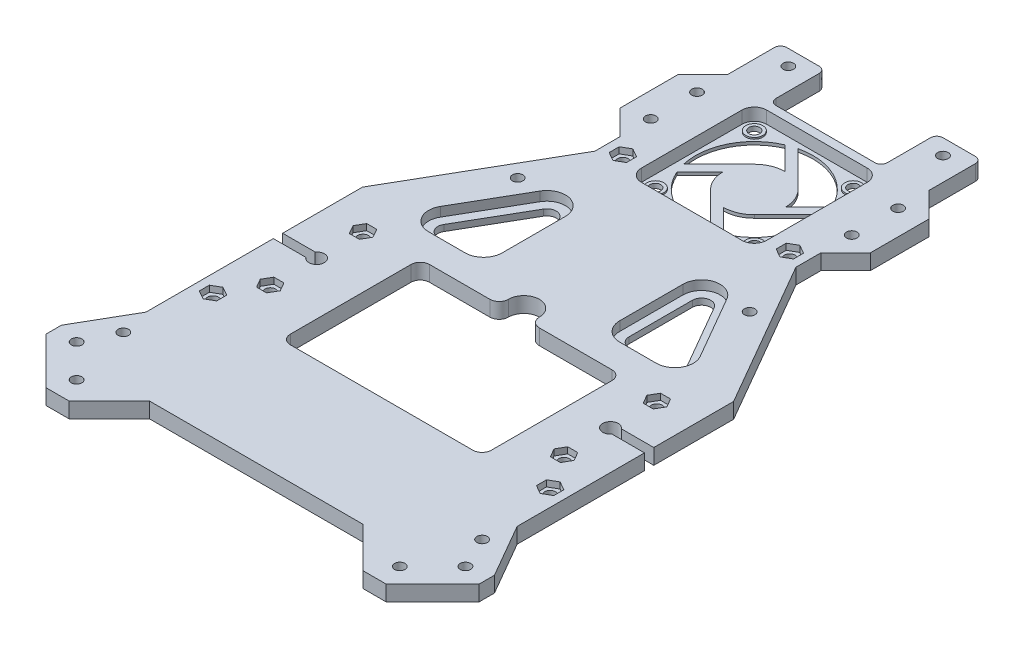
SolidWorks part; units mm, degrees
material "ABS PC"
ref_plane "Front Plane" through (0, 0, 0) normal (0, 0, 1) x (1, 0, 0)
ref_plane "Top Plane" through (0, 0, 0) normal (0, 1, 0) x (1, 0, 0)
ref_plane "Right Plane" through (0, 0, 0) normal (1, 0, 0) x (0, 0, -1)
sketch "Sketch1" plane through (0, 0, 0) normal (0, 1, 0) x (1, 0, 0)
  line L1 (70, -110) -> (-70, -110)
  line L2 (70, -110) -> (70, 110)
  line L3 (70, 110) -> (-70, 110)
  line L4 (-70, -110) -> (-70, 110)
  line L5 (70, -110) -> (-70, 110) construction
  line L6 (70, 110) -> (-70, -110) construction
  point P0 (0, 0)
  dimension "D1" = 220
  dimension "D2" = 140
extrude "Boss-Extrude1" add sketch "Sketch1" along normal blind 5
sketch "Sketch8" plane through (0, 5, 0) normal (0, 1, 0) x (1, 0, 0)
  line L0 (-70, 110) -> (-32.5, 110)
  line L1 (70, 110) -> (-70, 110) construction
  line L2 (-32.5, 110) -> (-32.5, 44.9519)
  line L3 (-32.5, 44.9519) -> (-70, -20)
  line L4 (-70, 110) -> (-70, -110) construction
  line L5 (-70, 110) -> (-70, -20)
  line L6 (0, 110) -> (0, -110) construction
  line L7 (-70, -110) -> (70, -110) construction
  line L8 (70, 110) -> (70, -20)
  line L9 (32.5, 44.9519) -> (70, -20)
  line L10 (32.5, 110) -> (32.5, 44.9519)
  line L11 (70, 110) -> (32.5, 110)
  dimension "D1" = 130
  dimension "D2" = 30
  dimension "D3" = 65
extrude "Cut-Extrude1" cut sketch "Sketch8" against normal blind 5
chamfer "Chamfer3" distance 15 angle 45 2 edges at (70, 2.5, 110) (-70, 2.5, 110)
sketch "Sketch48" plane through (0, 5, 0) normal (0, 1, 0) x (1, 0, 0)
  line L0 (32.5, 110) -> (-32.5, 110) construction
  line L1 (34.2449, 70.5) -> (40.5, 70.5) construction
  line L2 (32.5, 53) -> (32.5, 88)
  line L4 (32.5, 88) -> (40.5, 80)
  line L5 (40.5, 80) -> (40.5, 61)
  line L6 (32.5, 53) -> (40.5, 61)
  line L7 (0, 71.0199) -> (0, 60.9015) construction
  line L8 (-32.5, 53) -> (-40.5, 61)
  line L9 (-40.5, 80) -> (-40.5, 61)
  line L10 (-32.5, 88) -> (-40.5, 80)
  line L11 (-32.5, 53) -> (-32.5, 88)
  line L13 (32.5, 110) -> (32.5, 44.9519) construction
  point P16 (-32.5, 70.5)
  dimension "D1" = 45
  dimension "D2" = 8
  dimension "D3" = 35
  dimension "D4" = 39.5
extrude "Boss-Extrude4" add sketch "Sketch48" against normal up to surface (5 mm away) up to face at (0, 0, 14.0096)
sketch "Sketch10" plane through (0, 0, 0) normal (0, 1, 0) x (1, 0, 0)
  line L0 (0, 110) -> (0, -110) construction
  line L1 (32.5, 110) -> (-32.5, 110) construction
  line L2 (-55, -110) -> (55, -110) construction
  line L3 (-32.5, 78) -> (-32.5, 63) construction
  line L4 (-62.5, -102.5) -> (-57.5503, -97.5503) construction
  line L5 (-62.8536, -92.247) -> (-52.247, -102.8536) construction
  line L6 (-70, -95) -> (-55, -110) construction
  point P9 (32.5, 63)
  point P10 (32.5, 78)
  point P17 (52.247, -102.8536)
  point P18 (62.8536, -92.247)
  dimension "D1" = 15
  dimension "D2" = 65
  dimension "D3" = 32
  dimension "D4" = 15
  dimension "D5" = 7
sketch "Sketch15" plane through (0, 5, 0) normal (0, 1, 0) x (1, 0, 0)
  line L0 (0, 110) -> (0, -110) construction
  line L1 (32.5, 110) -> (-32.5, 110) construction
  line L2 (-55, -110) -> (55, -110) construction
  line L3 (25, 100) -> (-25, 100) construction
  line L4 (37.5, 25) -> (-37.5, 25) construction
  line L5 (58, -57) -> (-58, -57) construction
  point P9 (0, 100)
  point P13 (0, 25)
  point P15 (0, -57)
  dimension "D1" = 50
  dimension "D2" = 10
  dimension "D3" = 75
  dimension "D4" = 85
  dimension "D5" = 116
  dimension "D6" = 167
hole_wizard "CSK for M3 Flat Head Machine Screw3" positions "Sketch16" profile "Sketch17" countersink size "M3" standard "ANSI Metric"
sketch "Sketch16" plane through (0, 0, 0) normal (0, 1, 0) x (1, 0, 0)
  point P6 (37.5, 25)
  point P9 (-37.5, 25)
  point P12 (-25, 100)
  point P15 (25, 100)
sketch "Sketch17" plane through (37.5, 0, -25) normal (1, 0, 0) x (0, 0, -1)
  line L0 (0, 0) -> (0, 6.0215)
  line L1 (0, 6.0215) -> (1.7, 5)
  line L2 (1.7, 5) -> (1.7, 1.45)
  line L3 (1.7, 1.45) -> (3.15, 0)
  line L5 (3.15, 0) -> (0, 0)
  line L6 (-1.7, 1.45) -> (-3.15, 0) construction
  line L10 (0, 6.0215) -> (-1.7, 5) construction
  line L11 (0, -6.35) -> (0, 107.95) construction
  dimension "Hole Dia." = 3.4
  dimension "Hole Depth" = 5
  dimension "Near C'Sink Dia." = 6.3
  dimension "Near C'Sink Angle" = 90
  dimension "Drill Angle" = 118
sketch "Sketch18" plane through (0, 5, 0) normal (0, 1, 0) x (1, 0, 0)
  line L0 (32.5, 110) -> (-32.5, 110) construction
  line L1 (-46.4338, 114.6286) -> (34.8035, 114.6286)
  line L2 (-46.4338, 114.6286) -> (-46.4338, 105)
  line L3 (-46.4338, 105) -> (34.8035, 105)
  line L4 (34.8035, 114.6286) -> (34.8035, 105)
  dimension "D1" = 5
extrude "Cut-Extrude2" cut sketch "Sketch18" against normal blind 5
sketch "Sketch34" plane through (0, 5, 0) normal (0, 1, 0) x (1, 0, 0)
  line L0 (-70, -20) -> (-60, -2.6795)
  line L1 (-70, -20) -> (-32.5, 44.9519) construction
  line L2 (-60, -2.6795) -> (-60, -72.6795)
  line L3 (-60, -72.6795) -> (-70, -90)
  line L4 (-70, -20) -> (-70, -95) construction
  line L5 (-70, -90) -> (-70, -20)
  line L6 (0, -90.4055) -> (0, -61.6307) construction
  line L7 (70, -90) -> (70, -20)
  line L8 (60, -72.6795) -> (70, -90)
  line L9 (60, -2.6795) -> (60, -72.6795)
  line L10 (70, -20) -> (60, -2.6795)
  line L11 (-55, -110) -> (55, -110) construction
  dimension "D1" = 120
  dimension "D2" = 20
extrude "Cut-Extrude8" cut sketch "Sketch34" against normal blind 10
chamfer "Chamfer4" [suppressed] distance 20 angle 30
sketch "Sketch35" plane through (0, 5, 0) normal (0, 1, 0) x (1, 0, 0)
  line L1 (-30.5, -58.5) -> (34.5, -58.5)
  line L2 (-30.5, -58.5) -> (-30.5, -13.5)
  line L3 (-30.5, -13.5) -> (34.5, -13.5)
  line L4 (34.5, -58.5) -> (34.5, -13.5)
  line L5 (-30.5, -58.5) -> (34.5, -13.5) construction
  line L6 (-30.5, -13.5) -> (34.5, -58.5) construction
  point P0 (2, -36)
  dimension "D1" = 2
  dimension "D2" = 65
  dimension "D3" = 45
  dimension "D4" = 36
extrude "Cut-Extrude9" cut sketch "Sketch35" against normal through all
fillet "Fillet1" radius 3 4 edges at (-30.5, 2.5, 58.5) (-30.5, 2.5, 13.5) (34.5, 2.5, 13.5) (34.5, 2.5, 58.5)
sketch "Sketch36" plane through (0, 5, 0) normal (0, 1, 0) x (1, 0, 0)
  line L0 (0, -110) -> (0, -97) construction
  line L1 (-55, -110) -> (55, -110) construction
  line L2 (-47.5, -110) -> (-34.5, -97)
  line L3 (-34.5, -97) -> (34.5, -97)
  line L4 (-47.5, -110) -> (47.5, -110)
  line L6 (-70, -95) -> (-55, -110) construction
  line L7 (47.5, -110) -> (34.5, -97)
  dimension "D1" = 13
  dimension "D2" = 95
extrude "Cut-Extrude10" cut sketch "Sketch36" against normal through all
sketch "Sketch38" plane through (0, 0, 0) normal (0, -1, 0) x (1, 0, 0)
  line L0 (0, -105) -> (0, -90) construction
  line L1 (-32.5, -105) -> (32.5, -105) construction
  line L2 (18, -87) -> (-18, -87)
  line L3 (-18, -87) -> (-18, -105)
  line L4 (-18, -105) -> (18, -105)
  line L5 (18, -87) -> (18, -105)
  dimension "D1" = 90
  dimension "D2" = 18
  dimension "D3" = 36
extrude "Cut-Extrude14" cut sketch "Sketch38" against normal through all
sketch "Sketch39" plane through (0, 0, 0) normal (0, -1, 0) x (1, 0, 0)
  line L0 (0, 37.973) -> (0, 15.9654) construction
  circle A0 centre (-47.5, 30) radius 2.5
  circle A1 centre (47.5, 30) radius 2.5
  dimension "D1" = 95
  dimension "D2" = 5
  dimension "D3" = 30
extrude "Cut-Extrude15" cut sketch "Sketch39" against normal through all
hole_wizard "CSK for M3 Flat Head Machine Screw2" positions "Sketch40" profile "Sketch41" countersink size "M3" standard "ANSI Metric"
sketch "Sketch40" plane through (0, 0, 0) normal (0, -1, 0) x (-1, 0, 0)
  point P0 (-58, -82)
  point P3 (58, -82)
sketch "Sketch41" plane through (58, 0, 82) normal (1, 0, 0) x (0, 0, -1)
  line L0 (0, 0) -> (0, 11.0215)
  line L1 (0, 11.0215) -> (1.7, 10)
  line L2 (1.7, 10) -> (1.7, 1.45)
  line L3 (1.7, 1.45) -> (3.15, 0)
  line L5 (3.15, 0) -> (0, 0)
  line L6 (-1.7, 1.45) -> (-3.15, 0) construction
  line L10 (0, 11.0215) -> (-1.7, 10) construction
  line L11 (0, -6.35) -> (0, 107.95) construction
  dimension "Hole Dia." = 3.4
  dimension "Hole Depth" = 10
  dimension "Near C'Sink Dia." = 6.3
  dimension "Near C'Sink Angle" = 90
  dimension "Drill Angle" = 118
hole_wizard "Ø3.5 (3.5) Diameter Hole1" positions "Sketch45" profile "Sketch46" hole size "Ø3.5" standard "ANSI Metric"
sketch "Sketch45" plane through (0, 5, 0) normal (0, 1, 0) x (1, 0, 0)
  line L0 (-32.5, 44.9519) -> (-32.5, 53) construction
  line L1 (-60, -72.6795) -> (-60, -2.6795) construction
  line L2 (-32.5, 105) -> (-18, 105) construction
  point P0 (-54.5, -56.5)
  point P2 (-27, 48.5)
  dimension "D1" = 5.5
  dimension "D2" = 5.5
  dimension "D3" = 56.5
  dimension "D4" = 105
sketch "Sketch46" plane through (-54.5, 5, 56.5) normal (1, 0, 0) x (0, 0, 1)
  line L0 (0, 0) -> (0, 6.0515)
  line L1 (0, 6.0515) -> (1.75, 5)
  line L2 (1.75, 5) -> (1.75, 0)
  line L5 (1.75, 0) -> (0, 0)
  line L10 (0, 6.0515) -> (-1.75, 5) construction
  line L11 (0, -6.35) -> (0, 107.95) construction
  dimension "Hole Dia." = 3.5
  dimension "Hole Depth" = 5
  dimension "Drill Angle" = 118
mirror "Mirror1" about plane through (0, 0, 0) normal (1, 0, 0) of "Ø3.5 (3.5) Diameter Hole1"
sketch "Sketch47" plane through (0, 5, 0) normal (0, 1, 0) x (1, 0, 0)
  line L0 (0, 13.2168) -> (0, -3.9151) construction
  line L1 (29.8, 46.8834) -> (29.8, 50.1166)
  line L2 (29.8, 50.1166) -> (27, 51.7332)
  line L3 (27, 51.7332) -> (24.2, 50.1166)
  line L4 (24.2, 50.1166) -> (24.2, 46.8834)
  line L5 (24.2, 46.8834) -> (27, 45.2668)
  line L6 (27, 45.2668) -> (29.8, 46.8834)
  line L7 (57.3, -58.1166) -> (57.3, -54.8834)
  line L8 (57.3, -54.8834) -> (54.5, -53.2668)
  line L9 (54.5, -53.2668) -> (51.7, -54.8834)
  line L10 (51.7, -54.8834) -> (51.7, -58.1166)
  line L11 (51.7, -58.1166) -> (54.5, -59.7332)
  line L12 (54.5, -59.7332) -> (57.3, -58.1166)
  line L13 (-54.5, -59.7332) -> (-57.3, -58.1166)
  line L14 (-51.7, -58.1166) -> (-54.5, -59.7332)
  line L15 (-51.7, -54.8834) -> (-51.7, -58.1166)
  line L16 (-54.5, -53.2668) -> (-51.7, -54.8834)
  line L17 (-57.3, -54.8834) -> (-54.5, -53.2668)
  line L18 (-57.3, -58.1166) -> (-57.3, -54.8834)
  line L19 (-27, 45.2668) -> (-29.8, 46.8834)
  line L20 (-24.2, 46.8834) -> (-27, 45.2668)
  line L21 (-24.2, 50.1166) -> (-24.2, 46.8834)
  line L22 (-27, 51.7332) -> (-24.2, 50.1166)
  line L23 (-29.8, 50.1166) -> (-27, 51.7332)
  line L24 (-29.8, 46.8834) -> (-29.8, 50.1166)
  circle A0 centre (27, 48.5) radius 2.8 construction
  circle A1 centre (54.5, -56.5) radius 2.8 construction
  circle A2 centre (-54.5, -56.5) radius 2.8 construction
  circle A3 centre (-27, 48.5) radius 2.8 construction
  dimension "D1" = 5.6
extrude "Cut-Extrude16" cut sketch "Sketch47" against normal blind 2
hole_wizard "CSK for M3 Flat Head Machine Screw1" positions "Sketch52" profile "Sketch53" countersink size "M3" standard "ANSI Metric"
sketch "Sketch52" plane through (0, 0, 0) normal (0, -1, 0) x (-1, 0, 0)
  point P0 (32.5, 63)
  point P3 (32.5, 78)
  point P6 (-32.5, 78)
  point P9 (-32.5, 63)
  point P12 (62.8536, -92.247)
  point P15 (52.247, -102.8536)
  point P18 (-52.247, -102.8536)
  point P21 (-62.8536, -92.247)
sketch "Sketch53" plane through (-32.5, 0, -63) normal (1, 0, 0) x (0, 0, -1)
  line L0 (0, 0) -> (0, 6.0215)
  line L1 (0, 6.0215) -> (1.7, 5)
  line L2 (1.7, 5) -> (1.7, 1.45)
  line L3 (1.7, 1.45) -> (3.15, 0)
  line L5 (3.15, 0) -> (0, 0)
  line L6 (-1.7, 1.45) -> (-3.15, 0) construction
  line L10 (0, 6.0215) -> (-1.7, 5) construction
  line L11 (0, -6.35) -> (0, 107.95) construction
  dimension "Hole Dia." = 3.4
  dimension "Hole Depth" = 5
  dimension "Near C'Sink Dia." = 6.3
  dimension "Near C'Sink Angle" = 90
  dimension "Drill Angle" = 118
sketch "Sketch54" plane through (0, 5, 0) normal (0, 1, 0) x (1, 0, 0)
  line L0 (0, -24.4413) -> (0, -37.1235) construction
  circle A0 centre (-47.5, -30) radius 7.5
  circle A1 centre (-47.5, -30) radius 2.5
  circle A2 centre (-47.5, -30) radius 2.5 construction
  circle A3 centre (47.5, -30) radius 2.5
  circle A4 centre (47.5, -30) radius 7.5
  dimension "D1" = 15
extrude "Cut-Extrude17" [suppressed] cut sketch "Sketch54" against normal blind 2
hole_wizard "Ø3.5 (3.5) Diameter Hole2" positions "Sketch55" profile "Sketch56" hole size "Ø3.5" standard "ANSI Metric" end condition through all
sketch "Sketch55" plane through (0, 5, 0) normal (0, 1, 0) x (1, 0, 0)
  line L1 (16, 80) -> (-16, 80) construction
  line L2 (16, 80) -> (16, 48) construction
  line L3 (16, 48) -> (-16, 48) construction
  line L4 (-16, 80) -> (-16, 48) construction
  line L5 (0, 48) -> (0, 0) construction
  point P1 (16, 80)
  point P2 (-16, 48)
  point P5 (16, 48)
  point P6 (-16, 80)
  dimension "D1" = 32
  dimension "D2" = 48
sketch "Sketch56" plane through (16, 5, -80) normal (1, 0, 0) x (0, 0, 1)
  line L0 (0, 0) -> (0, 5)
  line L1 (0, 5) -> (1.75, 5)
  line L2 (1.75, 5) -> (1.75, 0)
  line L5 (1.75, 0) -> (0, 0)
  line L11 (0, -6.35) -> (0, 107.95) construction
  dimension "Thru Hole Dia." = 3.5
  dimension "Thru Hole Depth" = 5
sketch "Sketch57" plane through (0, 5, 0) normal (0, 1, 0) x (1, 0, 0)
  line L0 (-16, 80) -> (16, 48) construction
  line L1 (9.9995, 64.1) -> (17.4397, 71.5402)
  line L2 (7.0711, 56.9289) -> (18.4947, 68.3526)
  line L3 (0.1, 54.0005) -> (7.5402, 46.5603)
  line L4 (-7.0711, 56.9289) -> (4.3526, 45.5053)
  line L5 (-9.9995, 63.9) -> (-17.4397, 56.4598)
  line L6 (-7.0711, 71.0711) -> (-18.4947, 59.6474)
  line L7 (-0.1, 73.9995) -> (-7.5402, 81.4397)
  line L8 (7.0711, 71.0711) -> (-4.3526, 82.4947)
  line L9 (0, 58.5149) -> (0, 69.4851) construction
  circle A0 centre (0, 64) radius 19
  circle A1 centre (0, 64) radius 10
  point P31 (0, 64)
  dimension "D1" = 38
  dimension "D2" = 20
  dimension "D3" = 3
  dimension "D5" = 135
  dimension "D4" = 4
extrude "Cut-Extrude18" cut sketch "Sketch57" against normal blind 10 contours A1 L7 A0 L6 | A1 L1 A0 L8 | A1 L3 A0 L2 | A1 L5 A0 L4 region at (7.9912, 5, -75.4298) region at (11.4298, 5, -56.0088) region at (-11.4298, 5, -71.9912) region at (-7.9912, 5, -52.5702)
sketch "Sketch58" plane through (0, 5, 0) normal (0, 1, 0) x (1, 0, 0)
  line L1 (-16.25, 43.75) -> (16.25, 43.75)
  line L2 (-20.25, 47.75) -> (-20.25, 80.25)
  line L3 (-16.25, 84.25) -> (16.25, 84.25)
  line L4 (20.25, 47.75) -> (20.25, 80.25)
  line L5 (-20.25, 43.75) -> (20.25, 84.25) construction
  line L6 (-20.25, 84.25) -> (20.25, 43.75) construction
  arc A0 (-20.25, 47.75) -> (-16.25, 43.75) centre (-16.25, 47.75) ccw
  arc A1 (16.25, 43.75) -> (20.25, 47.75) centre (16.25, 47.75) ccw
  arc A2 (20.25, 80.25) -> (16.25, 84.25) centre (16.25, 80.25) ccw
  arc A3 (-16.25, 84.25) -> (-20.25, 80.25) centre (-16.25, 80.25) ccw
  point P0 (0, 64)
  dimension "D2" = 4
  dimension "D1" = 40.5
extrude "Cut-Extrude20" cut sketch "Sketch58" against normal blind 4
sketch "Sketch59" plane through (0, 0, 0) normal (0, -1, 0) x (1, 0, 0)
  line L0 (31.5, 13.5) -> (-27.5, 13.5) construction
  line L1 (5, 10.5) -> (-5, 10.5)
  line L2 (5, 10.5) -> (5, 13.5)
  line L3 (5, 13.5) -> (-5, 13.5)
  line L4 (-5, 10.5) -> (-5, 13.5)
  line L5 (5, 10.5) -> (-5, 13.5) construction
  line L6 (5, 13.5) -> (-5, 10.5) construction
  line L7 (0, 0) -> (0, 12) construction
  arc A0 (-5, 10.5) -> (5, 10.5) centre (0, 10.5) ccw
  point P0 (0, 12)
  dimension "D1" = 3
  dimension "D2" = 10
extrude "Cut-Extrude21" cut sketch "Sketch59" against normal blind 10 contours L4 L1 L2 L3 | L1 A0 region at (0, 0, 8.3779) region at (0, 0, 12)
fillet "Fillet5" radius 3 2 edges at (5, 2.5, 13.5) (-5, 2.5, 13.5)
sketch "Sketch60" plane through (0, 0, 0) normal (0, -1, 0) x (1, 0, 0)
  line L0 (-42, 1.5) -> (-22, 1.5)
  line L1 (-22, 1.5) -> (-22, -33.141)
  line L2 (-22, -33.141) -> (-42, 1.5)
  line L3 (0, 28.7462) -> (0, 44.2491) construction
  line L4 (22, -33.141) -> (42, 1.5)
  line L5 (22, 1.5) -> (22, -33.141)
  line L6 (42, 1.5) -> (22, 1.5)
  line L7 (-8, 13.5) -> (-27.5, 13.5) construction
  line L8 (-60, 2.6795) -> (-32.5, -44.9519) construction
  dimension "D1" = 20
  dimension "D2" = 44
  dimension "D3" = 12
extrude "Cut-Extrude22" cut sketch "Sketch60" against normal through all
fillet "Fillet6" radius 3 6 edges at (42, 2.5, 1.5) (22, 2.5, -33.141) (22, 2.5, 1.5) (-22, 2.5, 1.5) (-22, 2.5, -33.141) (-42, 2.5, 1.5)
fillet "Fillet7" radius 2 6 edges at (32.5, 2.5, -105) (-32.5, 2.5, -105) (18, 2.5, -105) (18, 2.5, -87) (-18, 2.5, -87) (-18, 2.5, -105)
sketch "Sketch61" plane through (0, 1, 0) normal (0, 1, 0) x (1, 0, 0)
  circle A1 centre (-16, 80) radius 2.75
  circle A2 centre (-16, 80) radius 1.75 construction
  circle A3 centre (16, 80) radius 2.75
  circle A4 centre (16, 48) radius 2.75
  circle A5 centre (-16, 48) radius 2.75
  circle A9 centre (-16, 80) radius 1.75
  circle A10 centre (-16, 80) radius 1.75
  circle A12 centre (16, 80) radius 1.75
  circle A13 centre (16, 80) radius 1.75
  circle A15 centre (16, 48) radius 1.75
  circle A16 centre (16, 48) radius 1.75
  circle A18 centre (-16, 48) radius 1.75
  circle A19 centre (-16, 48) radius 1.75
  dimension "D1" = 1
  dimension "D2" = 0
  dimension "D3" = 0
  dimension "D4" = 0
  dimension "D5" = 0
extrude "Boss-Extrude5" add sketch "Sketch61" along normal blind 0.5
sketch "Sketch62" plane through (0, 5, 0) normal (0, 1, 0) x (1, 0, 0)
  line L44 (0, 12.7981) -> (0, -1.7616) construction
  line L45 (36.8038, -4.5) -> (25, -4.5)
  line L46 (30.1962, 24.9449) -> (42, 4.5)
  line L47 (-19, 1.5) -> (-19, 21.9449)
  line L48 (-30.1962, 24.9449) -> (-42, 4.5)
  line L49 (-36.8038, -4.5) -> (-25, -4.5)
  line L50 (-19, 1.5) -> (-19, 21.9449)
  line L51 (-30.1962, 24.9449) -> (-42, 4.5)
  line L52 (-36.8038, -4.5) -> (-25, -4.5)
  line L53 (19, 1.5) -> (19, 21.9449)
  arc A13 (19, 21.9449) -> (30.1962, 24.9449) centre (25, 21.9449) cw
  arc A14 (42, 4.5) -> (36.8038, -4.5) centre (36.8038, 1.5) cw
  arc A15 (25, -4.5) -> (19, 1.5) centre (25, 1.5) cw
  arc A16 (-25, -4.5) -> (-19, 1.5) centre (-25, 1.5) ccw
  arc A17 (-42, 4.5) -> (-36.8038, -4.5) centre (-36.8038, 1.5) ccw
  arc A18 (-19, 21.9449) -> (-30.1962, 24.9449) centre (-25, 21.9449) ccw
  arc A19 (-25, -4.5) -> (-19, 1.5) centre (-25, 1.5) ccw
  arc A20 (-42, 4.5) -> (-36.8038, -4.5) centre (-36.8038, 1.5) ccw
  arc A21 (-19, 21.9449) -> (-30.1962, 24.9449) centre (-25, 21.9449) ccw
  dimension "D1" = 3
extrude "Cut-Extrude23" cut sketch "Sketch62" against normal blind 3
hole_wizard "Ø3.5 (3.5) Diameter Hole3" positions "Sketch64" profile "Sketch65" hole size "Ø3.5" standard "ANSI Metric" end condition through all
sketch "Sketch64" plane through (0, 0, 0) normal (0, -1, 0) x (-1, 0, 0)
  line L0 (47.5, -30) -> (47.5, -45) construction
  line L1 (47.5, -30) -> (45, -30) construction
  line L3 (0, -31.9374) -> (0, -51.0019) construction
  circle A0 centre (47.5, -30) radius 2.5 construction
  point P2 (47.5, -45)
  point P22 (47.5, -15)
  point P27 (0, 0)
  point P28 (-47.5, -15)
  point P29 (-47.5, -45)
  dimension "D1" = 30
sketch "Sketch65" plane through (47.5, 0, 45) normal (1, 0, 0) x (0, 0, -1)
  line L0 (0, 0) -> (0, 5)
  line L1 (0, 5) -> (1.75, 5)
  line L2 (1.75, 5) -> (1.75, 0)
  line L5 (1.75, 0) -> (0, 0)
  line L11 (0, -6.35) -> (0, 107.95) construction
  dimension "Thru Hole Dia." = 3.5
  dimension "Thru Hole Depth" = 5
sketch "Sketch66" plane through (0, 5, 0) normal (0, 1, 0) x (1, 0, 0)
  line L0 (-47.5, -30) -> (-38.51, -30) construction
  line L1 (-44.2668, -15) -> (-45.8834, -12.2)
  line L2 (-45.8834, -12.2) -> (-49.1166, -12.2)
  line L3 (-49.1166, -12.2) -> (-50.7332, -15)
  line L4 (-50.7332, -15) -> (-49.1166, -17.8)
  line L5 (-49.1166, -17.8) -> (-45.8834, -17.8)
  line L6 (-45.8834, -17.8) -> (-44.2668, -15)
  line L7 (-45.8834, -42.2) -> (-44.2668, -45)
  line L8 (-49.1166, -42.2) -> (-45.8834, -42.2)
  line L9 (-50.7332, -45) -> (-49.1166, -42.2)
  line L10 (-49.1166, -47.8) -> (-50.7332, -45)
  line L11 (-45.8834, -47.8) -> (-49.1166, -47.8)
  line L12 (-44.2668, -45) -> (-45.8834, -47.8)
  line L13 (0, -21.6578) -> (0, -42.5) construction
  line L14 (44.2668, -45) -> (45.8834, -47.8)
  line L15 (45.8834, -47.8) -> (49.1166, -47.8)
  line L16 (49.1166, -47.8) -> (50.7332, -45)
  line L17 (50.7332, -45) -> (49.1166, -42.2)
  line L18 (49.1166, -42.2) -> (45.8834, -42.2)
  line L19 (45.8834, -42.2) -> (44.2668, -45)
  line L20 (45.8834, -17.8) -> (44.2668, -15)
  line L21 (49.1166, -17.8) -> (45.8834, -17.8)
  line L22 (50.7332, -15) -> (49.1166, -17.8)
  line L23 (49.1166, -12.2) -> (50.7332, -15)
  line L24 (45.8834, -12.2) -> (49.1166, -12.2)
  line L25 (44.2668, -15) -> (45.8834, -12.2)
  circle A0 centre (-47.5, -15) radius 2.8 construction
  dimension "D1" = 5.6
extrude "Cut-Extrude24" cut sketch "Sketch66" against normal blind 2
sketch "Sketch67" plane through (0, 0, 0) normal (0, -1, 0) x (1, 0, 0)
  line L0 (-47.5, 30) -> (-60, 30) construction
  line L1 (-60, 72.6795) -> (-60, 2.6795) construction
  line L2 (-60, 31.5) -> (-49.5, 31.5)
  line L3 (-60, 31.5) -> (-60, 28.5)
  line L4 (-60, 28.5) -> (-49.5, 28.5)
  circle A0 centre (-47.5, 30) radius 2.5 construction
  circle A3 centre (-47.5, 30) radius 2.5
  circle A4 centre (-47.5, 30) radius 2.5
  dimension "D1" = 3
  dimension "D2" = 0
extrude "Cut-Extrude25" cut sketch "Sketch67" against normal through all contours A4 L0 L3 L4 | L0 A4 L2 L3 region at (-54.9193, 0, 29.244) region at (-54.9193, 0, 30.756)
mirror "Mirror2" about plane through (0, 0, 0) normal (1, 0, 0) of "Cut-Extrude25"
